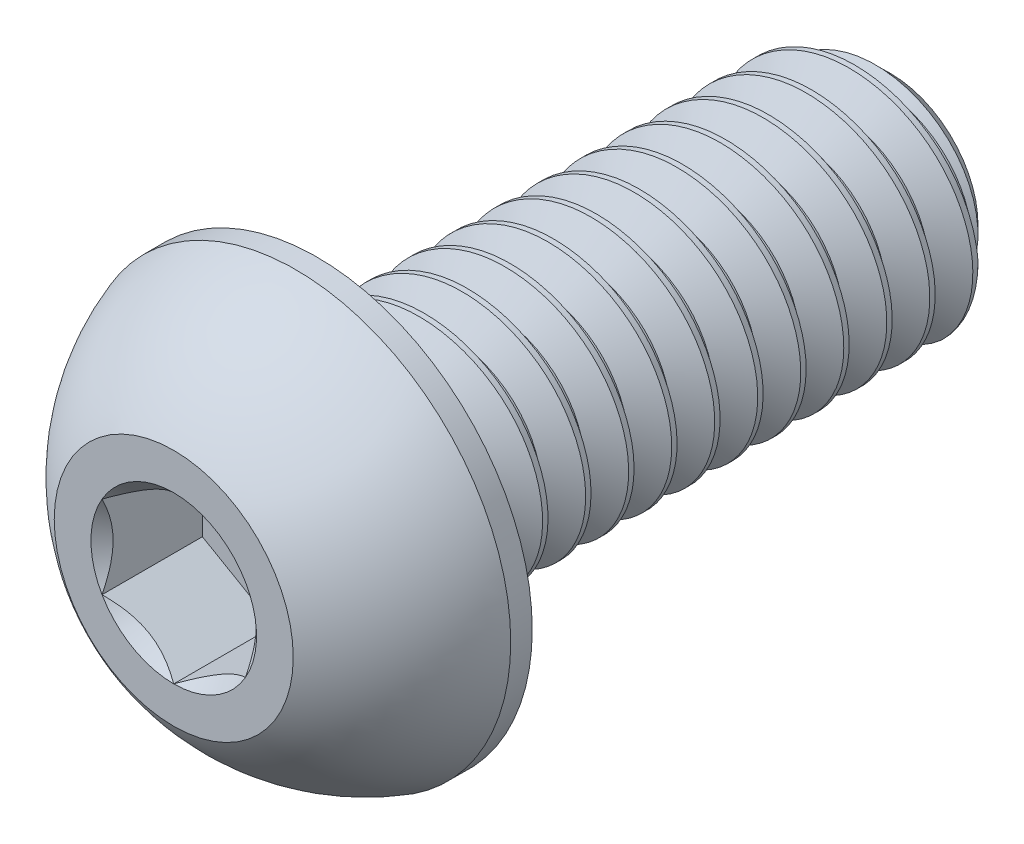
SolidWorks part; units mm, degrees
ref_plane "Front" through (0, 0, 0) normal (0, 0, 1) x (1, 0, 0)
ref_plane "Top" through (0, 0, 0) normal (0, 1, 0) x (1, 0, 0)
ref_plane "Right" through (0, 0, 0) normal (1, 0, 0) x (0, 0, -1)
sketch "Sketch1" plane through (0, 0, 0) normal (1, 0, 0) x (0, 0, -1)
  line L2 (1.5, 1.25) -> (7.5, 1.25)
  line L3 (7.5, 1.25) -> (7.5, 0)
  line L4 (7.5, 0) -> (1.5, 0)
  line L6 (1.275, 2.25) -> (1.5, 2.25) construction
  line L7 (7.5, 1.25) -> (7.5, -1.25) construction
  line L8 (0, 0) -> (1.5, 0) construction
  line L9 (1.5, 2.25) -> (1.5, -2.25) construction
  line L11 (1.5, 1.25) -> (1.5, 0)
  line L13 (0, 0.75) -> (0, -0.75) construction
  line L14 (0, 0.75) -> (0, 1.25) construction
  arc A3 (0, 1.25) -> (1.275, 2.25) centre (2.01, 0) cw construction
  dimension "D1" = 0.225
revolve "Revolve1" add sketch "Sketch1" angle 360 mid plane about L4
sketch "Sketch3" plane through (0, 0, -7.5) normal (0, 0, -1) x (-1, 0, 0)
  circle A0 centre (0, 0) radius 1.25
curve "Helix/Spiral1" pitch 0.45 height 6.45 radius 1.25 centre (0, 0, -7.5) axis (0, 0, 1) start towards (0, 1, 0)
sketch "Sketch2" plane through (0, 0, 0) normal (1, 0, 0) x (0, 0, -1)
  line L0 (7.5, 1.25) -> (7.8937, 1.25)
  line L1 (7.8937, 1.25) -> (7.725, 0.9577)
  line L2 (7.725, 0.9577) -> (7.6687, 0.9577)
  line L3 (7.6687, 0.9577) -> (7.5, 1.25)
  line L4 (7.5844, 1.1039) -> (7.8094, 1.1039) construction
  dimension "D1" = 60
  dimension "D2" = 0.0563
  dimension "D3" = 0.225
chamfer "Chamfer1" distance 0.3375 angle 45 1 edges at (0, 1.25, -7.5)
sweep "Cut-Sweep1" cut profiles "Sketch2" path "Helix/Spiral1" align with end faces yes
sketch "Sketch7" plane through (0, 0, 0) normal (1, 0, 0) x (0, 0, -1)
  line L6 (1.275, 2.25) -> (1.5, 2.25) construction
  line L8 (0, 0) -> (1.5, 0) construction
  line L11 (1.5, 2.25) -> (1.5, -2.25) construction
  line L12 (1.275, 2.25) -> (1.5, 2.25)
  line L13 (0, 0) -> (1.5, 0)
  line L14 (0, 0.75) -> (0, -0.75) construction
  line L15 (1.5, 2.25) -> (1.5, 0)
  line L16 (0, 1.25) -> (0, 0)
  arc A2 (1.275, 2.25) -> (0, 1.25) centre (2.01, 0) ccw construction
  arc A3 (1.275, 2.25) -> (0, 1.25) centre (2.01, 0) ccw
revolve "Revolve2" add sketch "Sketch7" angle 360 mid plane about L13
sketch "Sketch5" plane through (0, 0, 0) normal (0, 0, 1) x (1, 0, 0)
  line L1 (0.75, -0.433) -> (0.75, 0.433)
  line L2 (0.75, 0.433) -> (0, 0.866)
  line L3 (0, 0.866) -> (-0.75, 0.433)
  line L4 (-0.75, 0.433) -> (-0.75, -0.433)
  line L5 (-0.75, -0.433) -> (0, -0.866)
  line L6 (0, -0.866) -> (0.75, -0.433)
  circle A0 centre (0, 0) radius 0.75 construction
extrude "Cut-Extrude2" cut sketch "Sketch5" against normal blind 1.05
sketch "Sketch6" plane through (0, 0, 0) normal (0, 0, 1) x (1, 0, 0)
  circle A0 centre (0, 0) radius 0.866
extrude "Cut-Extrude3" cut sketch "Sketch6" against normal blind 1.05 draft 45
sketch "Sketch9" [suppressed] plane through (0, 0, -4.2164) normal (0, 0, 1) x (1, 0, 0)
  circle A2 centre (0, 0) radius 3.9687
extrude "Boss-Extrude2" [suppressed] add sketch "Sketch9" against normal offset from surface (9.525 mm away) 28.575 up to face at (0, 0.9125, -7.5)
sketch "Sketch10" plane through (0, 0, 0) normal (1, 0, 0) x (0, 0, -1)
  line L0 (7.5, 1.25) -> (7.5, -1.25) construction
  point P0 (6.825, -1.25)
  dimension "D1" = 0.675
equation "\"D3@Helix/Spiral1\" = \"Lg@Sketch1\" + \"D4@Helix/Spiral1\""
equation "\"D2@Sketch2\" = \"D4@Helix/Spiral1\" * .125"
equation "\"D3@Sketch2\" = \"D4@Helix/Spiral1\" * .5"
equation "\"D1@Chamfer1\" = \"D4@Helix/Spiral1\" * .75"
equation "\"D1@Cut-Extrude2\" = \"Head Ht@Sketch1\" * .7"
equation "\"D1@Sketch1\" = \"Head Ht@Sketch1\" * .15"
equation "\"D1@Sketch10\" = \"D4@Helix/Spiral1\" * 1.5"
equation "\"D1@Cut-Extrude3\" = \"D1@Cut-Extrude2\""
